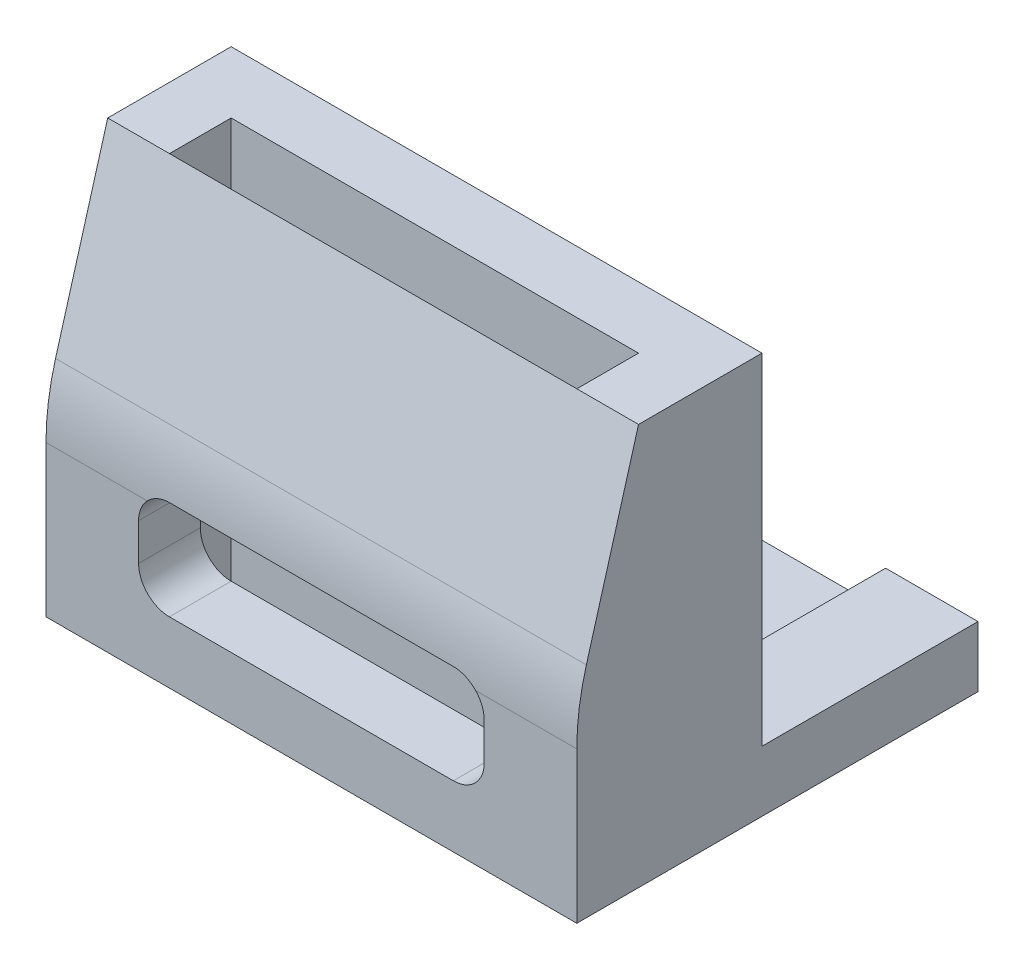
SolidWorks part; units mm, degrees
ref_plane "Front Plane" through (0, 0, 0) normal (0, 0, 1) x (1, 0, 0)
ref_plane "Top Plane" through (0, 0, 0) normal (0, 1, 0) x (1, 0, 0)
ref_plane "Right Plane" through (0, 0, 0) normal (1, 0, 0) x (0, 0, -1)
sketch "Sketch1" plane through (0, 0, 0) normal (0, 1, 0) x (1, 0, 0)
  line L0 (0, 0) -> (13.2, 0)
  line L1 (0, 0) -> (0, 2)
  line L2 (0, 2) -> (13.2, 2)
  line L3 (13.2, 2) -> (13.2, 0)
  line L4 (15.2, 4) -> (15.2, -2)
  line L5 (-2, -2) -> (15.2, -2)
  line L6 (-2, -2) -> (-2, 4)
  line L7 (-2, 4) -> (15.2, 4)
  dimension "D1" = 2
extrude "Boss-Extrude1" add sketch "Sketch1" along normal blind 13
sketch "Sketch2" plane through (0, 0, 2) normal (0, 0, 1) x (1, 0, 0)
  line L4 (2, 5.2) -> (11.2, 5.2)
  line L5 (1, 4.2) -> (1, 3)
  line L6 (2, 2) -> (11.2, 2)
  line L7 (12.2, 3) -> (12.2, 4.2)
  arc A1 (11.2, 2) -> (12.2, 3) centre (11.2, 3) ccw
  arc A2 (12.2, 4.2) -> (11.2, 5.2) centre (11.2, 4.2) ccw
  arc A3 (2, 5.2) -> (1, 4.2) centre (2, 4.2) ccw
  arc A4 (1, 3) -> (2, 2) centre (2, 3) ccw
  dimension "D1" = 1
extrude "Cut-Extrude1" cut sketch "Sketch2" against normal blind 13 contours L4 A2 L7 A1 L6 A4 L5 A3
sketch "Sketch4" plane through (0, 0, -4) normal (0, 0, -1) x (-1, 0, 0)
  line L0 (2, 13) -> (2, 0) construction
  line L1 (-15.2, 0) -> (2, 0)
  line L2 (-15.2, 0) -> (-15.2, 1.969)
  line L3 (-15.2, 1.969) -> (2, 1.969)
  line L4 (2, 0) -> (2, 1.969)
extrude "Boss-Extrude2" add sketch "Sketch4" along normal blind 7
sketch "Sketch5" plane through (0, 1.969, 0) normal (0, 1, 0) x (1, 0, 0)
  circle A0 centre (6.6, 7.5) radius 1.6
extrude "Cut-Extrude2" cut sketch "Sketch5" against normal blind 4
sketch "Sketch6" plane through (0, 0, -11) normal (0, 0, -1) x (-1, 0, 0)
  line L0 (-1, 4.2) -> (-1, 3) construction
  line L1 (-12.2065, 0.7524) -> (-1, 0.7524)
  line L2 (-12.2065, 0.7524) -> (-12.2065, 3.2384)
  line L3 (-12.2065, 3.2384) -> (-1, 3.2384)
  line L4 (-1, 0.7524) -> (-1, 3.2384)
extrude "Cut-Extrude3" cut sketch "Sketch6" against normal up to surface (7 mm away) up to face at (6.6, 3.6, -4)
sketch "Sketch7" plane through (15.2, 0, 0) normal (1, 0, 0) x (0, 0, -1)
  line L0 (0, 13) -> (-2, 6.0172)
  line L1 (-2, 13) -> (-2, 0) construction
  line L2 (-2, 6.0172) -> (-2, 13)
  line L3 (-2, 13) -> (0, 13)
extrude "Cut-Extrude4" cut sketch "Sketch7" against normal up to surface (17.2 mm away) up to face at (-2, 4.9897, -4.3333)
fillet "Fillet1" radius 8 1 edges at (6.6, 6.0172, 2)
